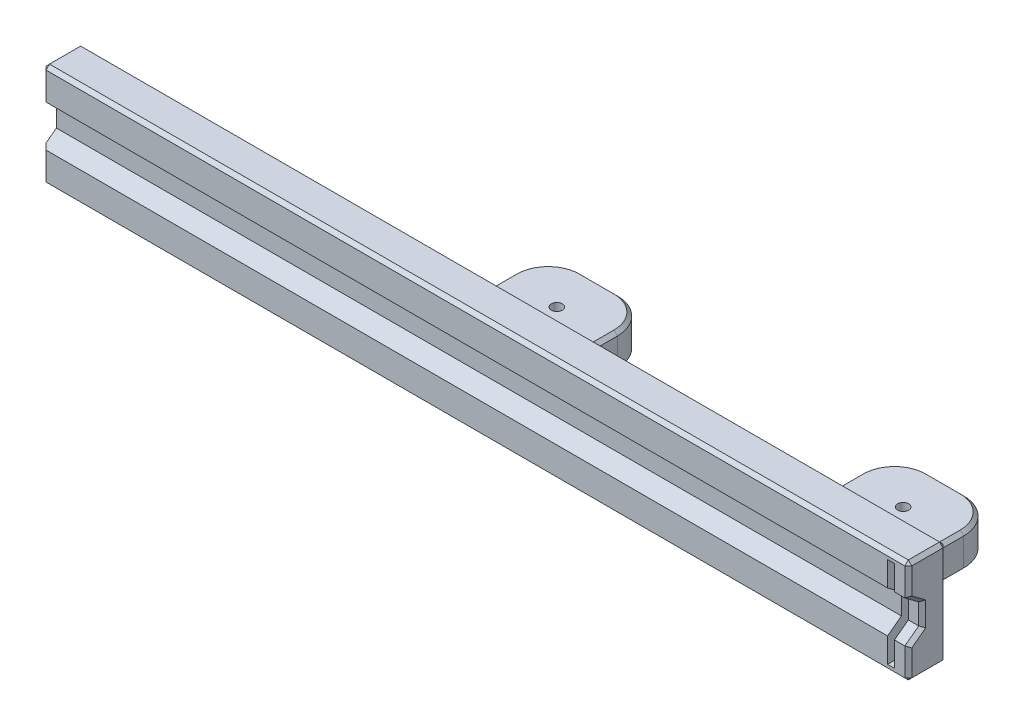
SolidWorks part; units mm, degrees
ref_plane "前基準面" through (0, 0, 0) normal (0, 0, 1) x (1, 0, 0)
ref_plane "上基準面" through (0, 0, 0) normal (0, 1, 0) x (1, 0, 0)
ref_plane "右基準面" through (0, 0, 0) normal (1, 0, 0) x (0, 0, -1)
sketch "草圖1" plane through (0, 0, 0) normal (0, 0, 1) x (1, 0, 0)
  line L0 (0, 0) -> (250, 0)
  line L1 (250, 0) -> (250, 30)
  line L2 (250, 30) -> (0, 30)
  line L3 (0, 30) -> (0, 0)
  dimension "D1" = 30
  dimension "D2" = 250
extrude "填料-伸長1" add sketch "草圖1" along normal blind 11
sketch "草圖4" plane through (0, 0, 0) normal (0, 0, -1) x (-1, 0, 0)
  line L0 (-250, 15) -> (0, 15)
  line L1 (-250, 0) -> (-250, 30) construction
  line L2 (0, 30) -> (0, 0) construction
  line L3 (-125, 30) -> (-125, 0)
  line L4 (-250, 30) -> (0, 30) construction
  line L5 (0, 0) -> (-250, 0) construction
  line L6 (-140, 15) -> (-125, 15)
  line L7 (-125, 15) -> (-110, 15)
  line L8 (-140, 15) -> (-140, 20)
  line L9 (-140, 20) -> (-110, 20)
  line L10 (-110, 20) -> (-110, 15)
  line L11 (-140, 15) -> (-140, 10)
  line L12 (-140, 10) -> (-125, 10)
  line L13 (-125, 10) -> (-110, 10)
  line L14 (-110, 10) -> (-110, 15)
  line L16 (-164.6389, 10) -> (-194.6389, 10)
  line L17 (-164.6389, 10) -> (-164.6389, 20)
  line L18 (-164.6389, 20) -> (-194.6389, 20)
  line L19 (-194.6389, 10) -> (-194.6389, 20)
  line L20 (-164.6389, 10) -> (-194.6389, 20) construction
  line L21 (-164.6389, 20) -> (-194.6389, 10) construction
  point P17 (-179.6389, 15)
  dimension "D1" = 15
  dimension "D2" = 15
  dimension "D3" = 5
  dimension "D4" = 5
  dimension "D5" = 10
  dimension "D6" = 30
extrude "填料-伸長2" add sketch "草圖4" along normal blind 25 contours L11 L12 L3 L0 | L9 L8 L0 L3 | L10 L9 L3 L0 | L13 L14 L0 L3 region at (132.5, 17.5, 0) region at (132.5, 12.5, 0) region at (117.5, 17.5, 0) region at (117.5, 12.5, 0)
sketch "草圖5" plane through (250, 0, 0) normal (1, 0, 0) x (0, 0, -1)
  line L0 (-11, 30) -> (-11, 21)
  line L1 (-11, 0) -> (-11, 30) construction
  line L2 (-7, 15) -> (-7, 12)
  line L3 (-7, 15) -> (-7, 18)
  line L4 (-7, 18) -> (-11, 21)
  line L5 (-11, 9) -> (-11, 0)
  line L6 (-11, 15) -> (0, 15)
  line L7 (0, 30) -> (0, 0) construction
  line L8 (-7, 12) -> (-11, 9)
  line L9 (-11, 9) -> (-11, 21)
  point P13 (0, 0)
  point P15 (0, 0)
  point P16 (0, 0)
  line M6 (-11, 30) -> (-11, 0)
  dimension "D1" = 12
  dimension "D2" = 30
  dimension "D3" = 6
  dimension "D4" = 3
  dimension "D5" = 3
  dimension "D6" = 4
extrude "除料-伸長2" cut sketch "草圖5" against normal through all contours L6 L3 L4 M6 | L8 L2 L6 M6 region at (250, 17.3333, 9.2222) region at (250, 12.6667, 9.2222)
sketch "草圖6" plane through (0, 10, 0) normal (0, -1, 0) x (1, 0, 0)
  line L0 (125, 0) -> (125, -25)
  line L1 (250, 0) -> (0, 0) construction
  line L2 (140, -25) -> (110, -25) construction
  line L3 (110, -12.5) -> (140, -12.5)
  line L4 (110, -25) -> (110, 0) construction
  line L5 (140, -25) -> (140, 0) construction
  circle A0 centre (125, -12.5) radius 1.6
  dimension "D1" = 3.2
extrude "除料-伸長3" cut sketch "草圖6" against normal through all contours L3 A0 L0 | L0 A0 L3 | L3 A0 L0 | L0 A0 L3 region at (125.6791, 10, -11.8209) region at (124.3209, 10, -11.8209) region at (125.6791, 10, -13.1791) region at (124.3209, 10, -13.1791)
sketch "草圖7" plane through (0, 10, 0) normal (0, -1, 0) x (1, 0, 0)
  line L0 (125, -14.1) -> (125, -25)
  line L1 (140, -25) -> (110, -25) construction
  circle A0 centre (125, -12.5) radius 1.6 construction
sketch "草圖9" plane through (0, 0, 0) normal (0, 0, -1) x (-1, 0, 0)
  line L1 (-194.6389, 20) -> (-164.6389, 20)
  line L2 (-194.6389, 20) -> (-194.6389, 10)
  line L3 (-194.6389, 10) -> (-164.6389, 10)
  line L4 (-164.6389, 20) -> (-164.6389, 10)
  line L5 (-194.6389, 20) -> (-164.6389, 10) construction
  line L6 (-194.6389, 10) -> (-164.6389, 20) construction
  point P0 (-179.6389, 15)
sketch "草圖11" plane through (0, 0, 0) normal (0, 0, -1) x (-1, 0, 0)
  line L0 (-125, 15) -> (-225, 15)
  line L1 (-250, 15) -> (0, 15) construction
  line L3 (-240, 10) -> (-210, 10)
  line L4 (-240, 10) -> (-240, 20)
  line L5 (-240, 20) -> (-210, 20)
  line L6 (-210, 10) -> (-210, 20)
  line L7 (-240, 10) -> (-210, 20) construction
  line L8 (-240, 20) -> (-210, 10) construction
  dimension "D1" = 100
  dimension "D2" = 10
  dimension "D3" = 30
extrude "填料-伸長4" add sketch "草圖11" along normal blind 25 contours L3 L6 L5 L4 region at (239.6838, 15, 0)
sketch "草圖12" plane through (0, 20, 0) normal (0, 1, 0) x (1, 0, 0)
  line L0 (240, 12.5) -> (210, 12.5)
  line L1 (240, 25) -> (240, 0) construction
  line L2 (210, 25) -> (210, 0) construction
  circle A0 centre (225, 12.5) radius 1.6
  dimension "D1" = 3.2
extrude "除料-伸長5" cut sketch "草圖12" against normal through all contours A0
fillet "圓角1" radius 10 4 edges at (110, 15, -25) (140, 15, -25) (210, 15, -25) (240, 15, -25)
sketch "草圖13" plane through (0, 0, 11) normal (0, 0, 1) x (1, 0, 0)
  line L1 (244, 28.1) -> (246, 28.1)
  line L2 (244, 28.1) -> (244, 1.9)
  line L3 (244, 1.9) -> (246, 1.9)
  line L4 (246, 28.1) -> (246, 1.9)
  line L5 (250, 15) -> (0, 15) construction
  line L6 (250, 0) -> (250, 30) construction
  dimension "D1" = 2
  dimension "D2" = 26.2
  dimension "D3" = 13.1
  dimension "D4" = 4
extrude "除料-伸長6" cut sketch "草圖13" against normal blind 7
chamfer "導角1" distance 1 angle 45 45 edges at (250, 15, 0) (250, 30, 5.5) (250, 0, 5.5) (125, 30, 11) (125, 0, 11) (0, 30, 5.5) (125, 30, 0) (125, 0, 0) (0, 15, 0) (0, 0, 5.5) (225, 10, -25) (225, 20, -25) (212.9289, 20, -22.0711) (212.9289, 10, -22.0711) (237.0711, 10, -22.0711) (237.0711, 20, -22.0711) (225, 20, 0) (210, 20, -7.5) (210, 15, 0) (210, 10, -7.5) (225, 10, 0) (240, 10, -7.5) (240, 15, 0) (240, 20, -7.5) (125, 20, -25) (125, 10, -25) (112.9289, 20, -22.0711) (112.9289, 10, -22.0711) (137.0711, 20, -22.0711) (137.0711, 10, -22.0711) (110, 20, -7.5) (125, 10, 0) (110, 10, -7.5) (110, 15, 0) (125, 20, 0) (140, 20, -7.5) (140, 15, 0) (140, 10, -7.5) (250, 4.5, 11) (250, 10.5, 9) (250, 15, 7) (250, 19.5, 9) (250, 25.5, 11) (0, 25.5, 11) (0, 4.5, 11)
